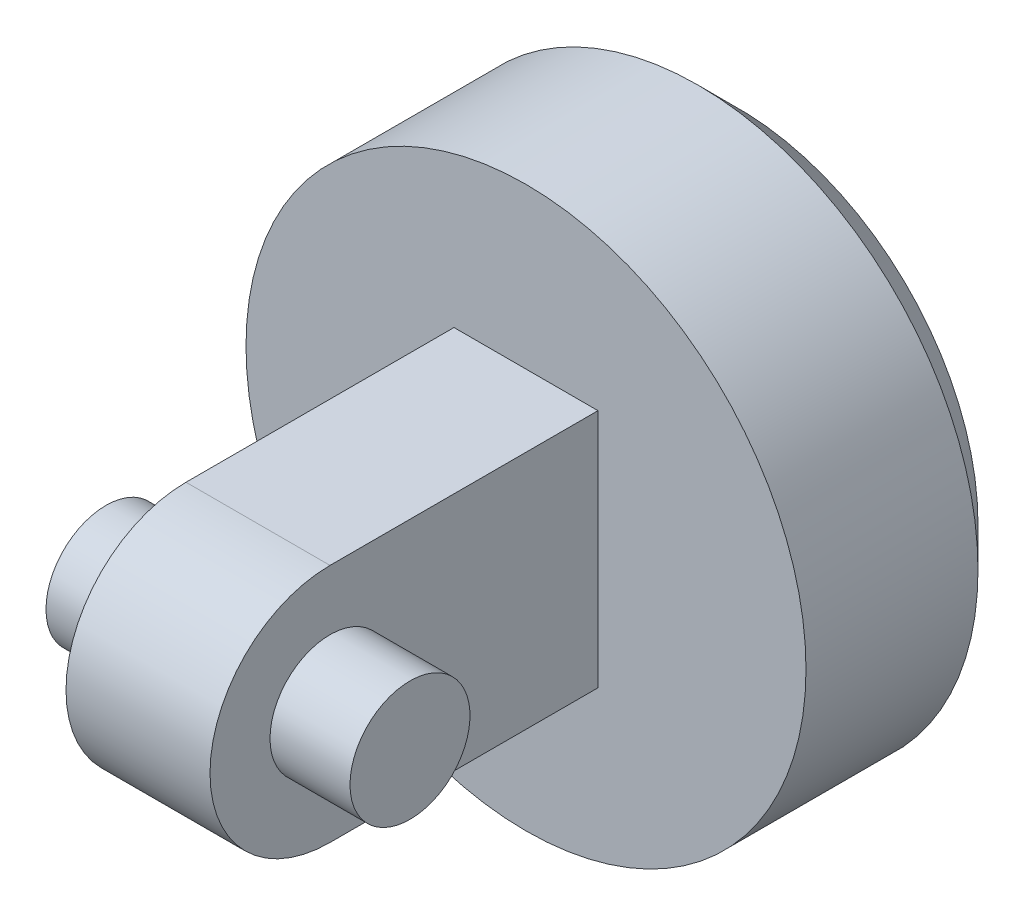
SolidWorks part; units mm, degrees
ref_plane "前视基准面" through (0, 0, 0) normal (0, 0, 1) x (1, 0, 0)
ref_plane "上视基准面" through (0, 0, 0) normal (0, 1, 0) x (1, 0, 0)
ref_plane "右视基准面" through (0, 0, 0) normal (1, 0, 0) x (0, 0, -1)
sketch "草图1" plane through (0, 0, 0) normal (0, 0, 1) x (1, 0, 0)
  circle A0 centre (0, 0) radius 7
  dimension "D1" = 14
extrude "凸台-拉伸1" add sketch "草图1" along normal blind 5.3
sketch "草图2" plane through (0, 0, 5.3) normal (0, 0, 1) x (1, 0, 0)
  line L1 (-1.8, -3) -> (1.8, -3)
  line L2 (-1.8, -3) -> (-1.8, 3)
  line L3 (-1.8, 3) -> (1.8, 3)
  line L4 (1.8, -3) -> (1.8, 3)
  line L5 (-1.8, -3) -> (1.8, 3) construction
  line L6 (-1.8, 3) -> (1.8, -3) construction
  point P0 (0, 0)
  dimension "D1" = 3.6
  dimension "D2" = 6
extrude "凸台-拉伸2" add sketch "草图2" along normal blind 9.7
sketch "草图3" plane through (-1.8, 0, 0) normal (-1, 0, 0) x (0, 0, 1)
  line L0 (15, 3) -> (15, -3) construction
  line L1 (12, -3) -> (12, 3) construction
  arc A0 (12, -3) -> (12, 3) centre (12, 0) ccw
extrude "切除-拉伸1" cut sketch "草图3" against normal through all and the other way through all flip side to cut
sketch "草图4" plane through (-1.8, 0, 0) normal (-1, 0, 0) x (0, 0, 1)
  circle A0 centre (12, 0) radius 1.5
  dimension "D1" = 3
chamfer "倒角1" distance 1 angle 45 1 edges at (7, 0, 0)
extrude "凸台-拉伸3" add sketch "草图4" along normal blind 2
mirror "镜向1" about plane through (0, 0, 0) normal (1, 0, 0) of "凸台-拉伸3"
